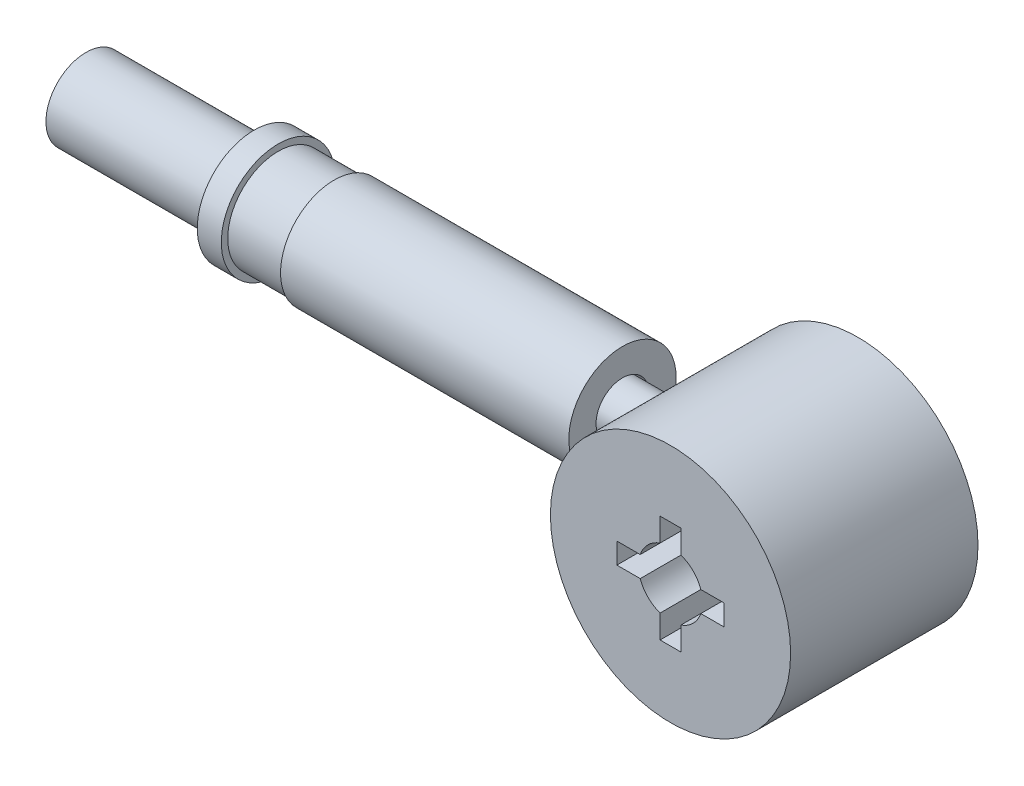
SolidWorks part; units mm, degrees
material "Простая углеродистая сталь"
ref_plane "Спереди" through (0, 0, 0) normal (0, 0, 1) x (1, 0, 0)
ref_plane "Сверху" through (0, 0, 0) normal (0, 1, 0) x (1, 0, 0)
ref_plane "Справа" through (0, 0, 0) normal (1, 0, 0) x (0, 0, -1)
sketch "Эскиз1" plane through (0, 0, 0) normal (0, 0, 1) x (1, 0, 0)
  line L0 (0, 0) -> (0, 2.5)
  line L1 (0, 2.5) -> (10.5, 2.5)
  line L2 (10.5, 2.5) -> (10.5, 3.55)
  line L3 (10.5, 3.55) -> (12, 3.55)
  line L4 (12, 3.55) -> (12, 3.15)
  line L5 (12, 3.15) -> (15.5, 3.15)
  line L6 (15.5, 3.15) -> (15.5, 1.55)
  line L7 (15.5, 1.55) -> (41, 1.55)
  line L8 (41, 1.55) -> (41, 0)
  line L9 (41, 0) -> (0, 0)
  line L10 (0, 0) -> (-3.9562, 0) construction
  dimension "D1" = 5
  dimension "D2" = 10.5
  dimension "D3" = 12
  dimension "D4" = 15.5
  dimension "D5" = 41
  dimension "D6" = 3.1
  dimension "D7" = 6.3
  dimension "D8" = 7.1
revolve "Повернуть1" add sketch "Эскиз1" angle 360 about L10
sketch "Эскиз2" plane through (15.5, 0, 0) normal (1, 0, 0) x (0, 0, -1)
  circle A0 centre (0, 0) radius 3.35
  circle A1 centre (0, 0) radius 1.65
  circle A2 centre (0, 0) radius 1.55 construction
  dimension "D1" = 0.1
  dimension "D2" = 6.7
extrude "Бобышка-Вытянуть1" add sketch "Эскиз2" along normal blind 18
sketch "Эскиз3" plane through (0, 0, 0) normal (0, 0, 1) x (1, 0, 0)
  line L0 (0, 0) -> (44.5, 0) construction
  line L1 (10.5, 2.5) -> (10.5, -2.5) construction
  circle A0 centre (44.5, 0) radius 7.5
  dimension "D2" = 15
  dimension "D1" = 34
extrude "Бобышка-Вытянуть2" add sketch "Эскиз3" against normal blind 11.7 from offset 8
sketch "Эскиз4" plane through (0, 0, 8) normal (0, 0, 1) x (1, 0, 0)
  circle A0 centre (44.5, 0) radius 2
  dimension "D1" = 4
extrude "Вырез-Вытянуть1" cut sketch "Эскиз4" against normal blind 5
sketch "Эскиз5" plane through (0, 0, 8) normal (0, 0, 1) x (1, 0, 0)
  line L0 (43.85, 0.65) -> (43.85, 3.35)
  line L1 (43.85, 3.35) -> (45.15, 3.35)
  line L2 (45.15, 3.35) -> (45.15, 0.65)
  line L3 (45.15, 0.65) -> (47.85, 0.65)
  line L4 (47.85, 0.65) -> (47.85, -0.65)
  line L5 (47.85, -0.65) -> (45.15, -0.65)
  line L6 (45.15, -0.65) -> (45.15, -3.35)
  line L7 (45.15, -3.35) -> (43.85, -3.35)
  line L8 (43.85, -3.35) -> (43.85, -0.65)
  line L9 (43.85, -0.65) -> (41.15, -0.65)
  line L10 (41.15, -0.65) -> (41.15, 0.65)
  line L11 (41.15, 0.65) -> (43.85, 0.65)
  line L12 (44.5, 0) -> (47.85, 0) construction
  line L13 (44.5, 0) -> (44.5, 3.35) construction
  line L14 (44.5, 0) -> (44.5, -3.35) construction
  line L15 (44.5, 0) -> (41.15, 0) construction
  dimension "D1" = 6.7
  dimension "D2" = 1.3
extrude "Вырез-Вытянуть2" cut sketch "Эскиз5" against normal blind 5
